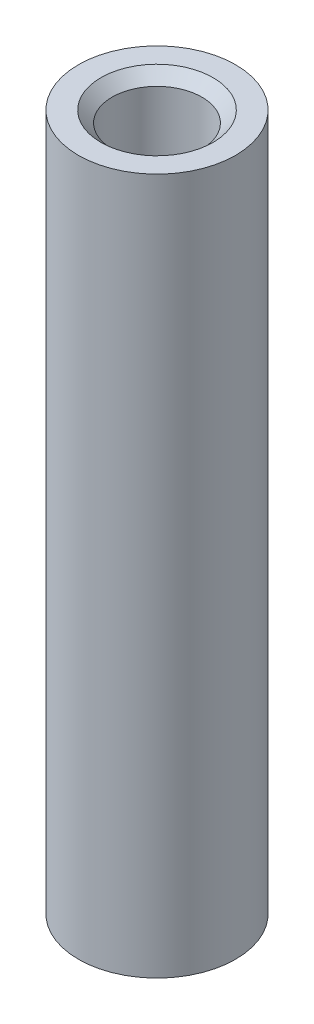
SolidWorks part; units mm, degrees
material "Natural Rubber"
ref_plane "Front Plane" through (0, 0, 0) normal (0, 0, 1) x (1, 0, 0)
ref_plane "Top Plane" through (0, 0, 0) normal (0, 1, 0) x (1, 0, 0)
ref_plane "Right Plane" through (0, 0, 0) normal (1, 0, 0) x (0, 0, -1)
sketch "Sketch1" plane through (0, 0, 0) normal (0, 1, 0) x (1, 0, 0)
  circle A0 centre (0, 0) radius 35
  circle A1 centre (0, 0) radius 20
  dimension "D1" = 70
  dimension "D2" = 40
extrude "Boss-Extrude1" add sketch "Sketch1" along normal blind 310.2
chamfer "Chamfer2" distance 5 angle 45 1 edges at (0, 310.2, 20)
